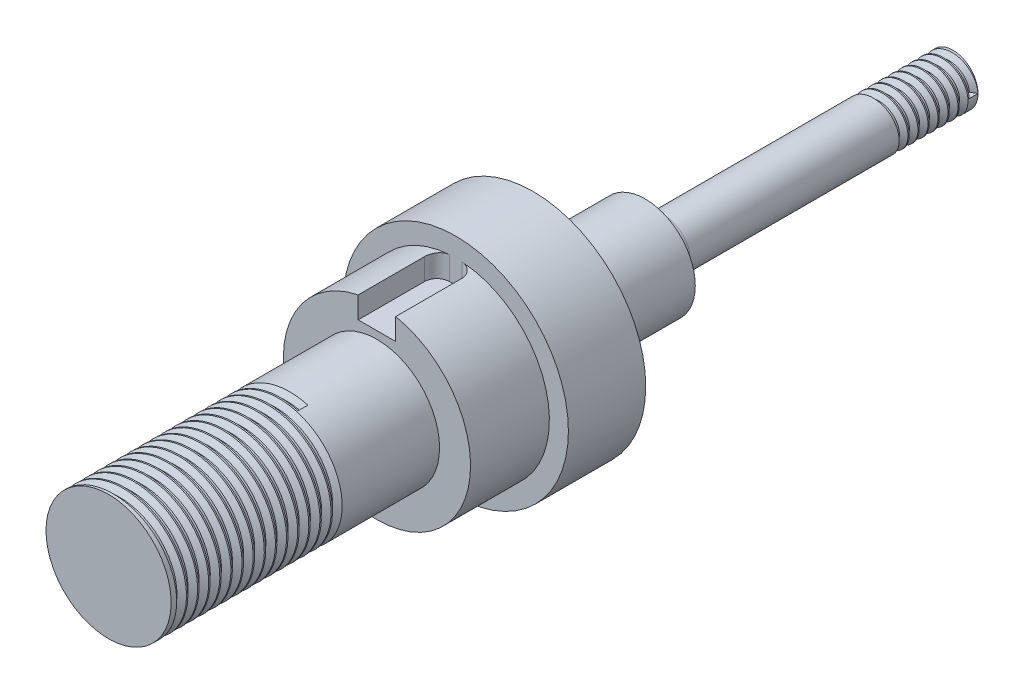
SolidWorks part; units mm, degrees
ref_plane "Front Plane" through (0, 0, 0) normal (0, 0, 1) x (1, 0, 0)
ref_plane "Top Plane" through (0, 0, 0) normal (0, 1, 0) x (1, 0, 0)
ref_plane "Right Plane" through (0, 0, 0) normal (1, 0, 0) x (0, 0, -1)
ref_plane "Plane7" through (0, 0, 53.86) normal (0, 0, 1) x (1, 0, 0)
sketch "Sketch1" plane through (0, 0, 0) normal (0, 0, 1) x (1, 0, 0)
  circle A0 centre (0, 0) radius 14.2875
  dimension "D1" = 28.575
extrude "Boss-Extrude1" add sketch "Sketch1" along normal blind 9.81
ref_plane "Plane4" through (0, 0, -53.265) normal (0, 0, -1) x (-1, 0, 0)
sketch "Sketch2" plane through (0, 0, 9.81) normal (0, 0, 1) x (1, 0, 0)
  circle A0 centre (0, 0) radius 11.8745
  dimension "D1" = 23.749
extrude "Boss-Extrude2" add sketch "Sketch2" along normal blind 10
sketch "Sketch3" plane through (0, 0, 19.81) normal (0, 0, 1) x (1, 0, 0)
  circle A0 centre (0, 0) radius 7.9375
  dimension "D1" = 15.875
extrude "Boss-Extrude3" add sketch "Sketch3" along normal up to surface (34.05 mm away) up to plane "Plane7"
ref_plane "Plane5" through (0, 0, 32.27) normal (0, 0, 1) x (1, 0, 0)
thread "Thread1" pitch 1.4111 method cut profile "Thread Profile1" start angle 0, offset 0, length 0, pitch 1.4111, diameter 15.875
ref_plane "Plane1" through (-7.9375, 0, 53.86) normal (0, -1, 0) x (-1, 0, 0)
sketch "Thread Profile1" plane through (-7.9375, 0, 53.86) normal (0, -1, 0) x (-1, 0, 0)
  line L0 (0, 0) -> (0, 1.4111) construction
  line L11 (0, 0) -> (0, 1.2347)
  line L12 (0, 1.2347) -> (-0.7638, 0.7937)
  line L13 (-0.7638, 0.7937) -> (-0.7638, 0.441)
  line L15 (-0.7638, 0.441) -> (0, 0)
  line L17 (-0.7638, 0.6174) -> (0, 0.6174) construction
  point P2 (0, 0)
  dimension "Pitch" = 1.4111
  dimension "Profile_Angle" = 60
  dimension "Profile_Land" = 0.3528
  dimension "Profile_Height" = 0.7638
sketch "Sketch8" plane through (0, 0, 0) normal (0, 0, -1) x (-1, 0, 0)
  circle A0 centre (0, 0) radius 3.175
  dimension "D1" = 6.35
extrude "Boss-Extrude4" add sketch "Sketch8" along normal up to surface (53.265 mm away) up to plane "Plane4"
sketch "Sketch10" plane through (0, 0, 0) normal (0, 0, -1) x (-1, 0, 0)
  circle A0 centre (0, 0) radius 5.08
  dimension "D1" = 10.16
ref_plane "Plane2" through (0, 0, -43.5775) normal (0, 0, -1) x (-1, 0, 0)
thread "Thread2" pitch 1.27 method cut profile "Thread Profile2" start angle 0, offset 0, length 0, pitch 1.27, diameter 6.35
ref_plane "Plane3" through (3.175, 0, -53.265) normal (0, -1, 0) x (1, 0, 0)
sketch "Thread Profile2" plane through (3.175, 0, -53.265) normal (0, -1, 0) x (1, 0, 0)
  line L0 (0, 0) -> (0, 1.27) construction
  line L11 (0, 0) -> (0, 1.1112)
  line L12 (0, 1.1112) -> (-0.6874, 0.7144)
  line L13 (-0.6874, 0.7144) -> (-0.6874, 0.3969)
  line L15 (-0.6874, 0.3969) -> (0, 0)
  line L17 (-0.6874, 0.5556) -> (0, 0.5556) construction
  point P2 (0, 0)
  dimension "Pitch" = 1.27
  dimension "Profile_Angle" = 60
  dimension "Profile_Land" = 0.3175
  dimension "Profile_Height" = 0.6874
sketch "Sketch14" plane through (0, 0, 19.81) normal (0, 0, 1) x (1, 0, 0)
  line L0 (-2.3813, 11.6333) -> (-2.3813, 8.89)
  line L1 (-2.3813, 8.89) -> (2.3813, 8.89)
  line L2 (2.3813, 8.89) -> (2.3813, 11.6333)
  arc A0 (-2.3813, 11.6333) -> (2.3813, 11.6333) centre (0, 0) cw
  circle A1 centre (0, 0) radius 11.8745 construction
  point P6 (0, 8.89)
  point P9 (0, 11.8745)
  dimension "D1" = 4.7625
  dimension "D2" = 2.9845
extrude "Cut-Extrude1" cut sketch "Sketch14" against normal up to surface (10 mm away) up to face at (11.8745, 0, 9.81)
sketch "Sketch15" plane through (0, 0, 0) normal (0, 0, -1) x (-1, 0, 0)
  circle A0 centre (0, 0) radius 6.35
  dimension "D1" = 12.7
extrude "Boss-Extrude5" add sketch "Sketch15" along normal blind 14.224
fillet "Fillet1" radius 2.54 1 edges at (-3.175, 0, -14.224) first distance on face at (-3.175, 0, -14.224)
fillet "Fillet2" radius 1.5875 2 edges at (2.3813, 10.2616, 9.81) (-2.3813, 10.2616, 9.81)
ref_plane "Plane6" through (0, 0, 0) normal (0, 0, 1) x (1, 0, 0)
